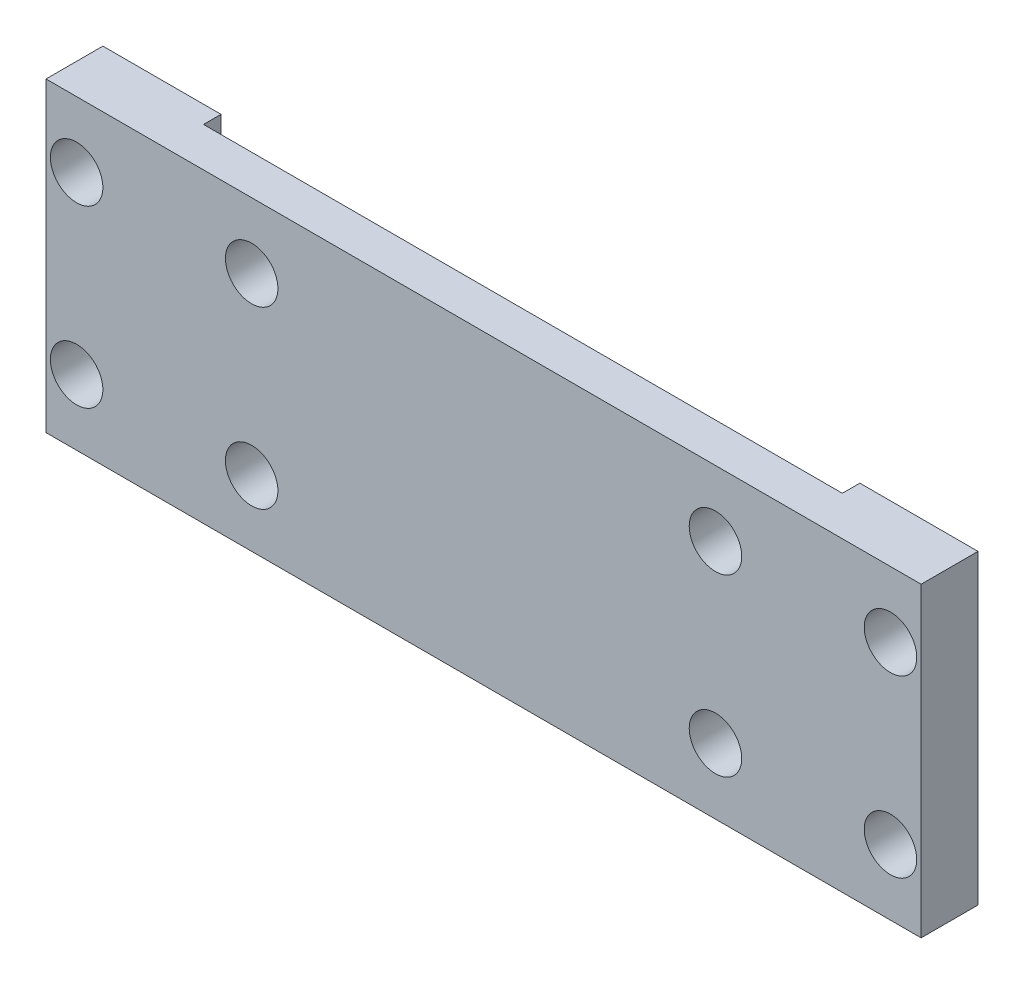
SolidWorks part; units mm, degrees
ref_plane "Plan de face" through (0, 0, 0) normal (0, 0, 1) x (1, 0, 0)
ref_plane "Plan de dessus" through (0, 0, 0) normal (0, 1, 0) x (1, 0, 0)
ref_plane "Plan de droite" through (0, 0, 0) normal (1, 0, 0) x (0, 0, -1)
sketch "Esquisse1" plane through (0, 0, 0) normal (0, 0, 1) x (1, 0, 0)
  line L0 (-36.5, 0) -> (36.5, 0) construction
  line L1 (-36.5, 0) -> (-50, 0)
  line L2 (-36.5, 0) -> (-36.5, -35)
  line L3 (-36.5, -35) -> (-50, -35)
  line L4 (-50, 0) -> (-50, -35)
  line L9 (-50, -17.5) -> (-36.5, -17.5) construction
  line L10 (-46.5, -7.5) -> (-46.5, -27.5) construction
  line L11 (0, 0) -> (0, -35) construction
  line L12 (36.5, -35) -> (50, -35)
  line L13 (50, 0) -> (50, -35)
  line L14 (36.5, 0) -> (50, 0)
  line L15 (36.5, 0) -> (36.5, -35)
  circle A0 centre (-46.5, -7.5) radius 1.75
  circle A1 centre (-46.5, -27.5) radius 1.75
  circle A2 centre (46.5, -27.5) radius 1.75
  circle A3 centre (46.5, -7.5) radius 1.75
  point P8 (0, 0)
  point P15 (-46.5, -17.5)
  dimension "D3" = 3.5
  dimension "D1" = 73
  dimension "D2" = 13.5
  dimension "D4" = 20
  dimension "D5" = 35
  dimension "D6" = 3.5
extrude "Boss.-Extru.1" add sketch "Esquisse1" along normal blind 2
sketch "Esquisse2" plane through (0, 0, 2) normal (0, 0, 1) x (1, 0, 0)
  line L0 (0, 0) -> (0, -35) construction
  line L1 (-50, 0) -> (50, 0)
  line L2 (-50, 0) -> (-50, -35)
  line L3 (-50, -35) -> (50, -35)
  line L4 (50, 0) -> (50, -35)
  line L5 (-26.5, -7.5) -> (-26.5, -27.5) construction
  line L6 (-26.5, -7.5) -> (-46.5, -7.5) construction
  circle A0 centre (-46.5, -7.5) radius 3
  circle A1 centre (-46.5, -27.5) radius 3
  circle A2 centre (46.5, -7.5) radius 3
  circle A3 centre (46.5, -27.5) radius 3
  circle A4 centre (-26.5, -7.5) radius 3
  circle A5 centre (-26.5, -27.5) radius 3
  circle A6 centre (26.5, -27.5) radius 3
  circle A7 centre (26.5, -7.5) radius 3
  point P25 (-23.5248, -30.8042)
  dimension "D1" = 6
  dimension "D2" = 20
  dimension "D3" = 20
extrude "Boss.-Extru.2" add sketch "Esquisse2" along normal blind 4.5
